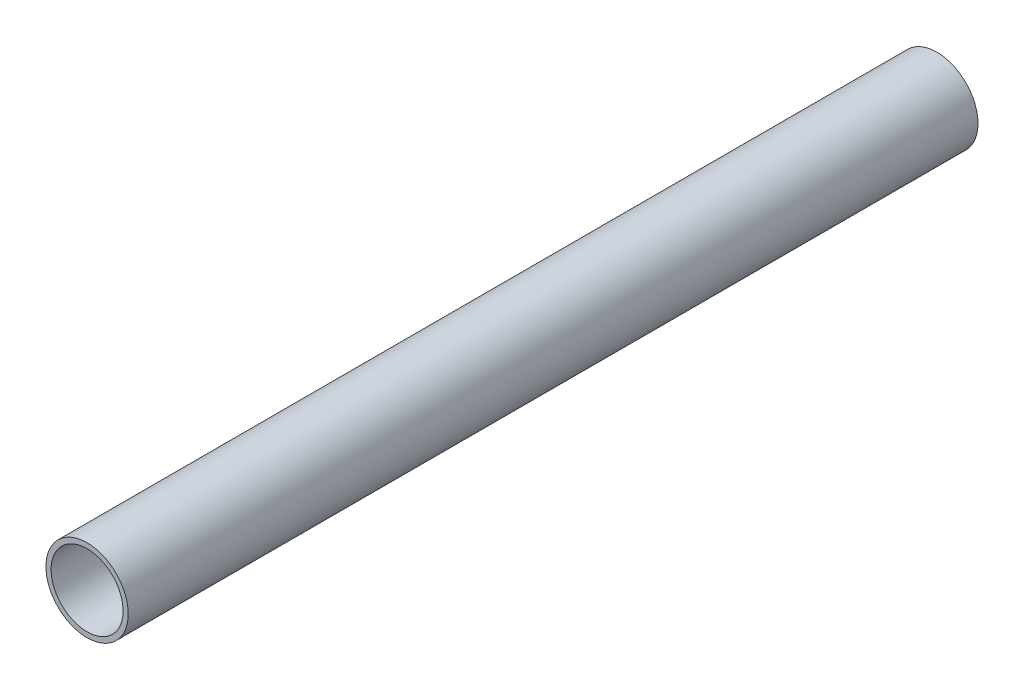
SolidWorks part; units mm, degrees
material "PC High Viscosity"
ref_plane "Front Plane" through (0, 0, 0) normal (0, 0, 1) x (1, 0, 0)
ref_plane "Top Plane" through (0, 0, 0) normal (0, 1, 0) x (1, 0, 0)
ref_plane "Right Plane" through (0, 0, 0) normal (1, 0, 0) x (0, 0, -1)
sketch "Sketch1" plane through (0, 0, 0) normal (0, 0, 1) x (1, 0, 0)
  circle A0 centre (0, 0) radius 12.7
  circle A1 centre (0, 0) radius 11.1125
  dimension "D1" = 25.4
  dimension "D2" = 1.5875
extrude "Boss-Extrude1" add sketch "Sketch1" along normal blind 262.18
